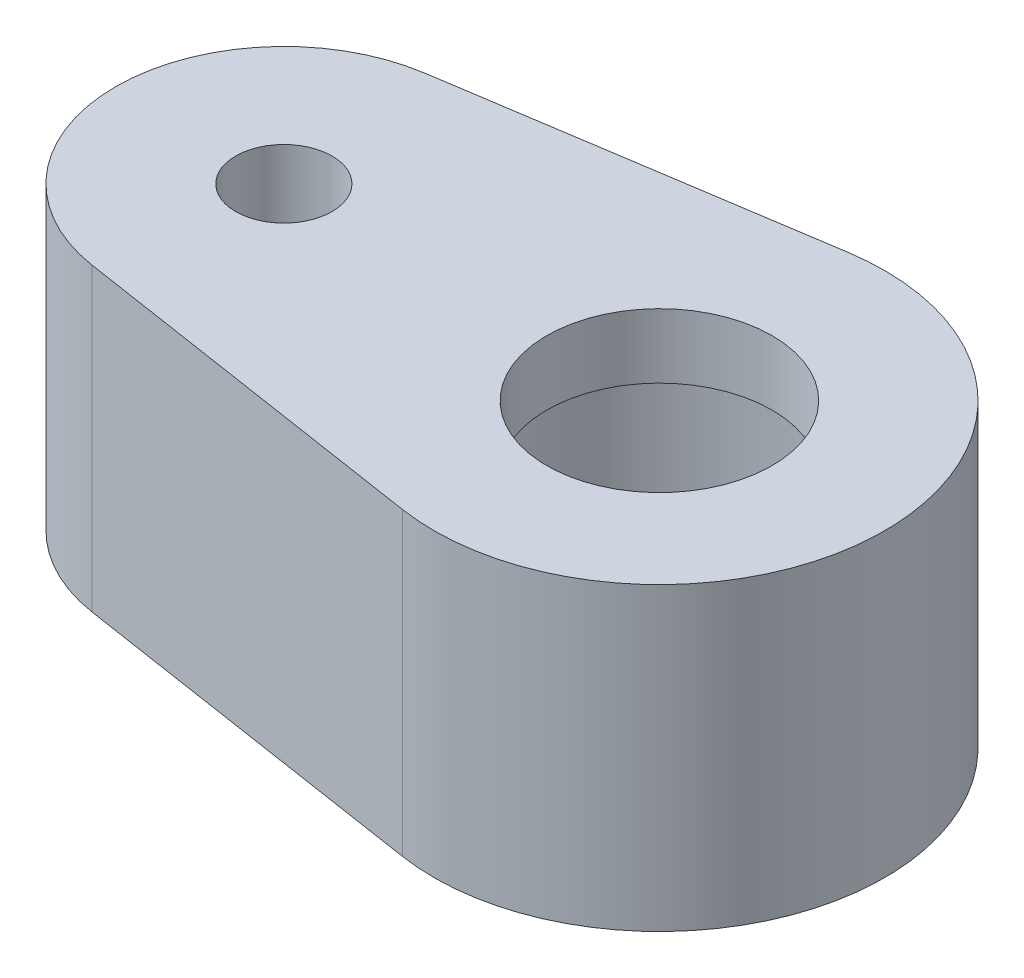
SolidWorks part; units mm, degrees
ref_plane "Front Plane" through (0, 0, 0) normal (0, 0, 1) x (1, 0, 0)
ref_plane "Top Plane" through (0, 0, 0) normal (0, 1, 0) x (1, 0, 0)
ref_plane "Right Plane" through (0, 0, 0) normal (1, 0, 0) x (0, 0, -1)
sketch "Sketch1" plane through (0, 0, 0) normal (0, 1, 0) x (1, 0, 0)
  line L0 (-2.6702, 1.107) -> (-0.228, 1.4826)
  line L1 (-2.6702, -1.107) -> (-0.228, -1.4826)
  line L2 (-2.5, 0) -> (0, 0) construction
  arc A0 (-0.228, -1.4826) -> (-0.228, 1.4826) centre (0, 0) ccw
  arc A1 (-2.6702, 1.107) -> (-2.6702, -1.107) centre (-2.5, 0) ccw
  dimension "D1" = 2.24
  dimension "D2" = 3
  dimension "D3" = 2.5
extrude "Boss-Extrude1" add sketch "Sketch1" along normal blind 1 and the other way blind 1
sketch "Sketch4" plane through (0, 0, 0) normal (0, 0, 1) x (1, 0, 0)
  line L0 (1.145, 0) -> (1.145, 0.465)
  line L1 (1.145, 0.465) -> (0.75, 0.5708)
  line L2 (0.75, 0.5708) -> (0.75, 1)
  line L3 (1.5, 1) -> (-0.228, 1) construction
  line L4 (0, 0) -> (1.145, 0) construction
  line L5 (1.145, 0) -> (1.145, -0.465)
  line L6 (1.145, -0.465) -> (0.75, -0.5708)
  line L7 (-0.228, -1) -> (1.5, -1) construction
  line L9 (0, -1) -> (0, 1)
  line L10 (0, 1) -> (0.75, 1)
  line L11 (0.75, -0.5708) -> (0.75, -1)
  line L12 (0, -1) -> (0.75, -1)
  dimension "D1" = 0.465
  dimension "D2" = 105
  dimension "D3" = 1.145
  dimension "D4" = 0.75
revolve "Cut-Revolve1" cut sketch "Sketch4" angle 360 about L9
sketch "Sketch5" plane through (0, 1, 0) normal (0, 1, 0) x (1, 0, 0)
  circle A0 centre (-2.5, 0) radius 0.3207
  dimension "D1" = 0.6414
extrude "Cut-Extrude1" cut sketch "Sketch5" against normal up to next
